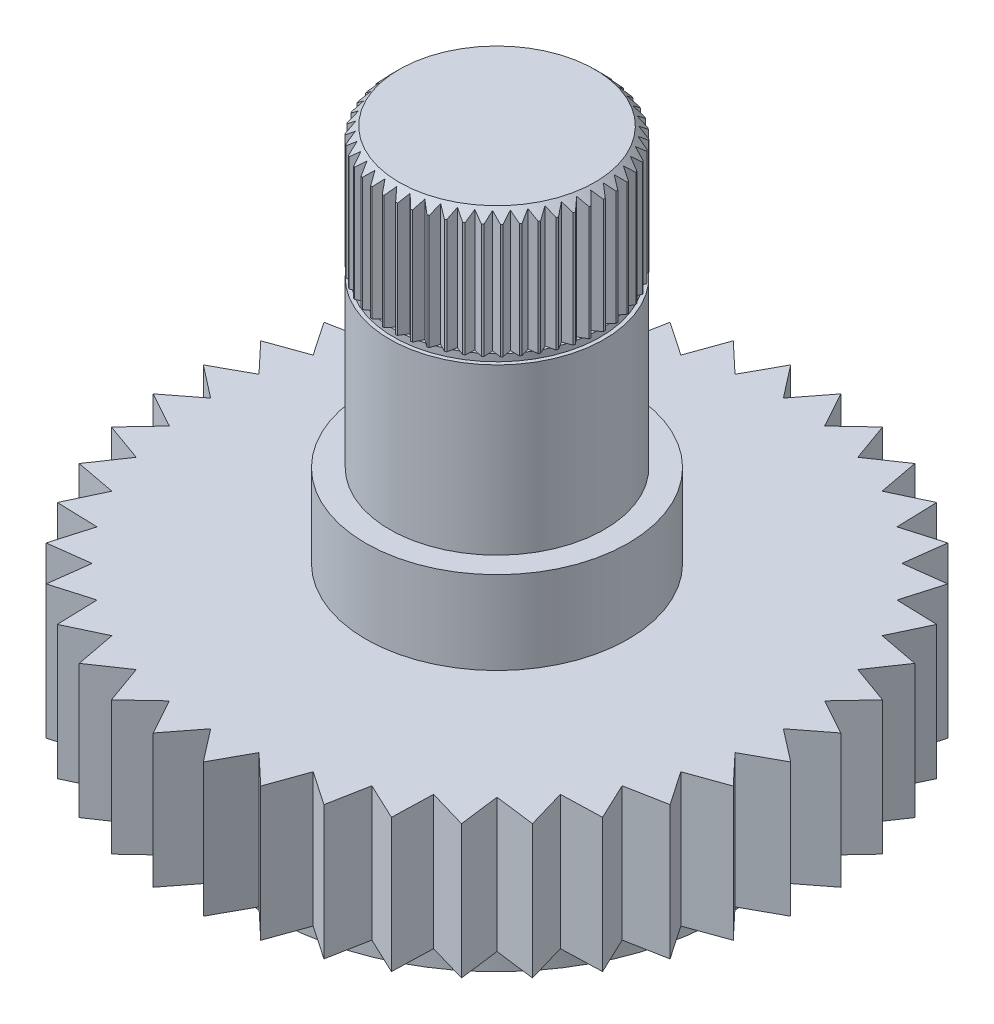
SolidWorks part; units mm, degrees
material "Chrome Stainless Steel"
ref_plane "Front Plane" through (0, 0, 0) normal (0, 0, 1) x (1, 0, 0)
ref_plane "Top Plane" through (0, 0, 0) normal (0, 1, 0) x (1, 0, 0)
ref_plane "Right Plane" through (0, 0, 0) normal (1, 0, 0) x (0, 0, -1)
sketch "Sketch1" plane through (0, 0, 0) normal (0, 0, 1) x (1, 0, 0)
  line L0 (0, 0) -> (0, 35.5657) construction
  line L1 (6.016, 0) -> (8.509, 0)
  line L2 (8.509, 0) -> (8.509, 3.556)
  line L3 (8.509, 3.556) -> (3.4925, 3.556)
  line L4 (2.8575, 5.7658) -> (2.8575, 10.1501)
  line L5 (2.8575, 13.6398) -> (0, 13.6398)
  line L6 (0, 13.6398) -> (0, 0.9398)
  line L7 (0, 0.9398) -> (5, 0.9398)
  line L8 (5, 0.9398) -> (5, -1.6002)
  line L9 (2.8575, 10.3378) -> (2.7555, 10.3378)
  line L10 (2.7555, 10.3378) -> (2.7555, 10.1501)
  line L11 (2.7555, 10.1501) -> (2.8575, 10.1501)
  line L12 (2.8575, 10.3378) -> (2.8575, 13.6398)
  line L13 (2.8575, 5.7658) -> (3.4925, 5.7658)
  line L14 (3.4925, 5.7658) -> (3.4925, 3.556)
  line L15 (6.016, 0) -> (6.016, -1.6002)
  line L16 (6.016, -1.6002) -> (5, -1.6002)
  dimension "D1" = 5.715
  dimension "D2" = 10
  dimension "D3" = 17.018
  dimension "D4" = 3.556
  dimension "D5" = 15.24
  dimension "D6" = 2.54
  dimension "D7" = 7.366
  dimension "D8" = 6.985
  dimension "D9" = 1.6002
  dimension "D10" = 1.016
  dimension "D11" = 3.302
revolve "Revolve1" add sketch "Sketch1" angle 360 about L0
sketch "Sketch2" plane through (0, 0.9398, 0) normal (0, -1, 0) x (1, 0, 0)
  line L0 (0, 1.5875) -> (0, -1.5875)
  arc A0 (0, 1.5875) -> (0, -1.5875) centre (0, 0) cw
  dimension "D1" = 1.5875
extrude "Cut-Extrude1" cut sketch "Sketch2" against normal blind 2.032
sketch "Sketch3" plane through (0, 3.556, 0) normal (0, 1, 0) x (-1, 0, 0)
  line L0 (0.6676, -8.4828) -> (0, -7.62)
  line L1 (0, -7.62) -> (-0.6676, -8.4828)
  line L2 (-0.6676, -8.4828) -> (-1.192, -7.5262) construction
  line L3 (-1.192, -7.5262) -> (0, 0) construction
  line L4 (0, 0) -> (-0.6676, -8.4828) construction
  line L5 (0, -7.62) -> (0, 0) construction
  circle A0 centre (0, 0) radius 8.509 construction
  arc A1 (-0.6676, -8.4828) -> (0.6676, -8.4828) centre (0, 0) ccw
  circle A2 centre (0, 0) radius 7.62 construction
  dimension "D2" = 15.24
  dimension "D1" = 9
extrude "Cut-Extrude2" cut sketch "Sketch3" against normal through all
pattern_circular "CirPattern1" count 40 over 360 about axis through (0, 0, 0) along (0, 1, 0) of "Cut-Extrude2"
chamfer "Chamfer1" distance 0.254 angle 45 1 edges at (0, 13.6398, -2.8575)
sketch "Sketch4" plane through (0, 13.6398, 0) normal (0, 1, 0) x (-1, 0, 0)
  line L0 (0.1555, -2.8533) -> (0, -2.667)
  line L1 (0, -2.667) -> (-0.1555, -2.8533)
  line L2 (-0.1555, -2.8533) -> (-0.2898, -2.6512) construction
  line L3 (-0.2898, -2.6512) -> (0, 0) construction
  line L4 (0, 0) -> (-0.1555, -2.8533) construction
  line L5 (0, -2.667) -> (0, 0) construction
  circle A0 centre (0, 0) radius 2.8575 construction
  circle A1 centre (0, 0) radius 2.667 construction
  arc A2 (-0.1555, -2.8533) -> (0.1555, -2.8533) centre (0, 0) ccw
  dimension "D2" = 5.334
  dimension "D1" = 6.238
extrude "Cut-Extrude3" cut sketch "Sketch4" against normal up to surface (3.302 mm away) up to face at (0, 10.3378, -2.8575)
pattern_circular "CirPattern2" count 50 over 360 about axis through (0, 0, 0) along (0, 1, 0) of "Cut-Extrude3"
ref_axis "Axis1" through (0, -31.0516, 0) along (0, 1, 0)
equation "\"D1@Sketch3\"=360/\"D1@CirPattern1\""
